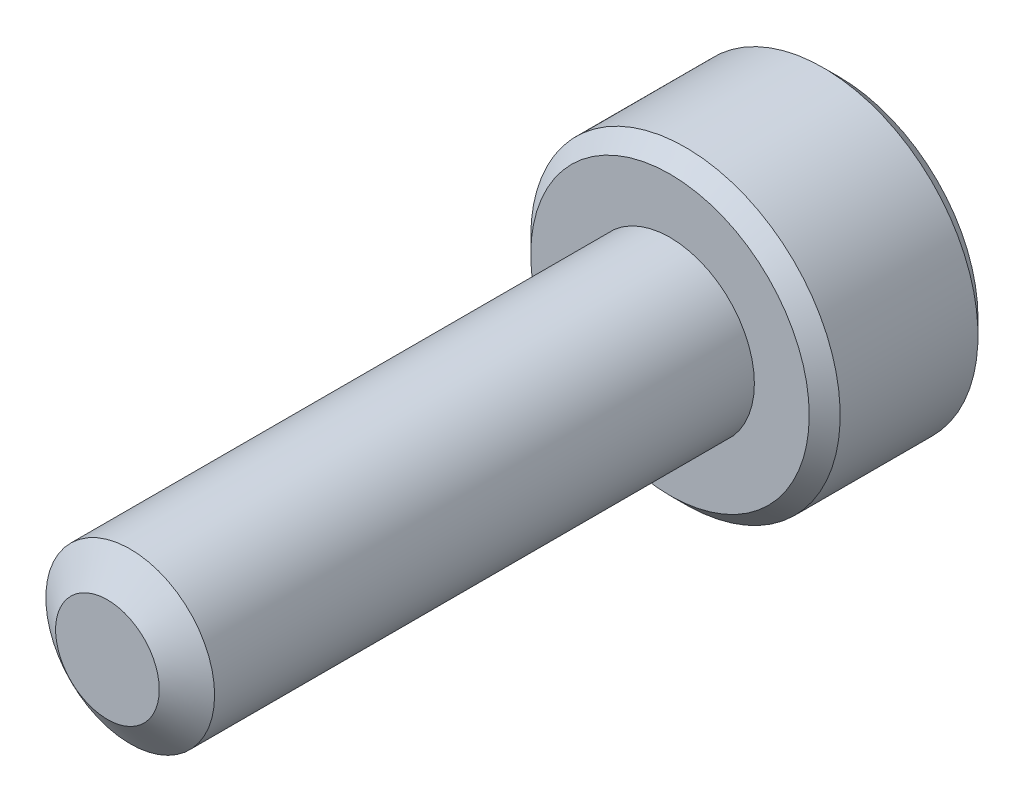
SolidWorks part; units mm, degrees
other "DetailItem1"
material "1.4310 (X10CrNi18-8)"
ref_plane "Front Plane" through (0, 0, 0) normal (0, 0, 1) x (1, 0, 0)
ref_plane "Top Plane" through (0, 0, 0) normal (0, 1, 0) x (1, 0, 0)
ref_plane "Right Plane" through (0, 0, 0) normal (1, 0, 0) x (0, 0, -1)
sketch "Sketch1" plane through (0, 0, 0) normal (0, 0, 1) x (1, 0, 0)
  circle A0 centre (0, 0) radius 1.5
  dimension "OD" = 3
extrude "Extrude1" add sketch "Sketch1" against normal blind 10
sketch "Sketch2" plane through (0, 0, 0) normal (0, 0, 1) x (1, 0, 0)
  circle A0 centre (0, 0) radius 1.5 construction
  circle A1 centre (0, 0) radius 1.5
curve "Helix/Spiral1" pitch 0.5 height 10.5 turns 21 parameters "pitch"=0.5
sketch "Sketch3" plane through (0, 0, 0) normal (1, 0, 0) x (0, 0, -1)
  line L0 (-0.4375, 1.5) -> (-0.25, 1.1752)
  line L1 (-0.25, 1.1752) -> (-0.1875, 1.1752)
  line L2 (-0.1875, 1.1752) -> (0, 1.5)
  line L3 (-0.4375, 1.5) -> (0, 1.5)
  line L4 (-0.2187, 1.5) -> (-0.2188, 1.1752) construction
  line L5 (-0.3438, 1.3376) -> (-0.0938, 1.3376) construction
  line L6 (0, 1.5) -> (0, -1.5) construction
  dimension "D1" = 0.0625
  dimension "D2" = 0.25
  dimension "D3" = 60
sweep "Cut-Sweep1" [suppressed] cut profiles "Sketch3" path "Helix/Spiral1"
sketch "Sketch4" plane through (0, 0, 0) normal (1, 0, 0) x (0, 0, -1)
  line L0 (0.4053, 1.5) -> (0, 0.9212)
  line L1 (0, 0.9212) -> (0, 1.5)
  line L2 (0.4053, 1.5) -> (0, 1.5)
  line L3 (-0.4375, 1.5) -> (0, 1.5) construction
  line L4 (0, 0) -> (7.0209, 0) construction
  dimension "D1" = 55
  dimension "D2" = 0.254
revolve "Cut-Revolve1" cut sketch "Sketch4" angle 360 about L4
sketch "Sketch6" plane through (0, 0, -10) normal (0, 0, -1) x (-1, 0, 0)
  circle A0 centre (0, 0) radius 2.75
  dimension "head dia" = 5.5
extrude "Extrude2" add sketch "Sketch6" along normal blind 3
sketch "Sketch7" plane through (0, 0, -13) normal (0, 0, -1) x (-1, 0, 0)
  line L1 (0, 1.4434) -> (-1.25, 0.7217)
  line L2 (-1.25, 0.7217) -> (-1.25, -0.7217)
  line L3 (-1.25, -0.7217) -> (0, -1.4434)
  line L4 (0, -1.4434) -> (1.25, -0.7217)
  line L5 (1.25, -0.7217) -> (1.25, 0.7217)
  line L6 (1.25, 0.7217) -> (0, 1.4434)
  circle A0 centre (0, 0) radius 1.25 construction
  dimension "hex dia" = 2.5
extrude "Cut-Extrude1" cut sketch "Sketch7" against normal blind 1.875
sketch "Sketch8" plane through (0, 0, -13) normal (0, 0, -1) x (-1, 0, 0)
  circle A0 centre (0, 0) radius 1.4434
extrude "Cut-Extrude2" cut sketch "Sketch8" against normal through all draft 45
chamfer "Chamfer1" distance 0.275 angle 45 2 edges at (-2.75, 0, -13) (-2.75, 0, -10)
sketch "Sketch10" plane through (0, 0, -10) normal (0, 0, 1) x (1, 0, 0)
  circle A1 centre (0, 0) radius 1.5
  circle A2 centre (0, 0) radius 1.5
  dimension "D1" = 0
ref_plane "Plane1" through (0, 0, 0) normal (0, 0, 1) x (1, 0, 0)
extrude "partial thread" [suppressed] add sketch "Sketch10" along normal up to surface (4 mm away) separate body up to plane "Plane1"
chamfer "Chamfer2" [suppressed] distance 0.06 angle 45
combine bodies "Combine1" [suppressed] operation type add bodies to combine 107 108
sketch "Sketch9" plane through (0, 0, 0) normal (1, 0, 0) x (0, 0, -1)
  line L0 (0, 1.5) -> (0, -1.5) construction
  line L1 (1.25, 1.5) -> (1.25, -1.5) construction
  dimension "D1" = 1.25
equation "\"D3@Helix/Spiral1\" = \"screw length@Extrude1\"+\"pitch@Helix/Spiral1\""
equation "\"D1@Sketch3\" = \"pitch@Helix/Spiral1\"*.125"
equation "\"D2@Sketch3\" = \"pitch@Helix/Spiral1\"*.5"
equation "\"D1@Cut-Extrude1\" = \"hex dia@Sketch7\"*.75"
equation "\"D1@Chamfer1\" = \"head dia@Sketch6\"*.05"
equation "\"D1@Sketch9\" = \"pitch@Helix/Spiral1\"*2.5"
equation "\"D1@Chamfer2\"=\"OD@Sketch1\"*.02"
